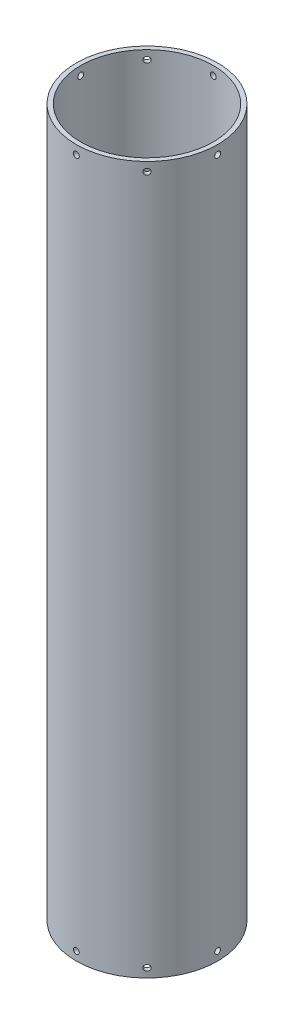
SolidWorks part; units mm, degrees
material "6061-T6 (SS)"
ref_plane "Front Plane" through (0, 0, 0) normal (0, 0, 1) x (1, 0, 0)
ref_plane "Top Plane" through (0, 0, 0) normal (0, 1, 0) x (1, 0, 0)
ref_plane "Right Plane" through (0, 0, 0) normal (1, 0, 0) x (0, 0, -1)
sketch "Sketch1" plane through (0, 0, 0) normal (0, 1, 0) x (1, 0, 0)
  circle A0 centre (0, 0) radius 76.2
  circle A1 centre (0, 0) radius 71.4375
  dimension "D1" = 152.4
  dimension "D2" = 142.875
extrude "Inner&OuterDiameter" add sketch "Sketch1" along normal blind 762
sketch "Sketch2" plane through (0, 0, 0) normal (0, 0, 1) x (1, 0, 0)
  line L0 (71.4375, 762) -> (-71.4375, 762) construction
  line L1 (-76.2, 0) -> (76.2, 0) construction
  circle A0 centre (0, 752.475) radius 3.175
  circle A1 centre (0, 9.525) radius 3.175
  dimension "D2" = 6.35
  dimension "D3" = 6.35
  dimension "D1" = 9.525
  dimension "D4" = 9.525
extrude "Top&BottomBoltHoles" cut sketch "Sketch2" against normal through all
pattern_circular "CirPattern1" count 8 over 360 about axis through (0, 762, 0) along (0, -1, 0) of "Top&BottomBoltHoles"
